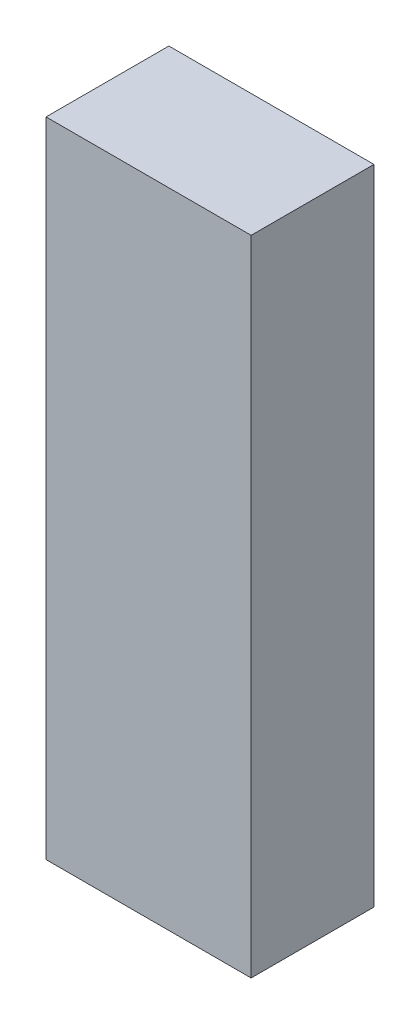
SolidWorks part; units mm, degrees
ref_plane "Front Plane" through (0, 0, 0) normal (0, 0, 1) x (1, 0, 0)
ref_plane "Top Plane" through (0, 0, 0) normal (0, 1, 0) x (1, 0, 0)
ref_plane "Right Plane" through (0, 0, 0) normal (1, 0, 0) x (0, 0, -1)
sketch "Sketch1" plane through (0, 0, 0) normal (0, 1, 0) x (1, 0, 0)
  line L1 (0, 0) -> (40.4939, 0)
  line L2 (0, 0) -> (0, 24.2514)
  line L3 (0, 24.2514) -> (40.4939, 24.2514)
  line L4 (40.4939, 0) -> (40.4939, 24.2514)
extrude "Boss-Extrude1" add sketch "Sketch1" along normal blind 127
